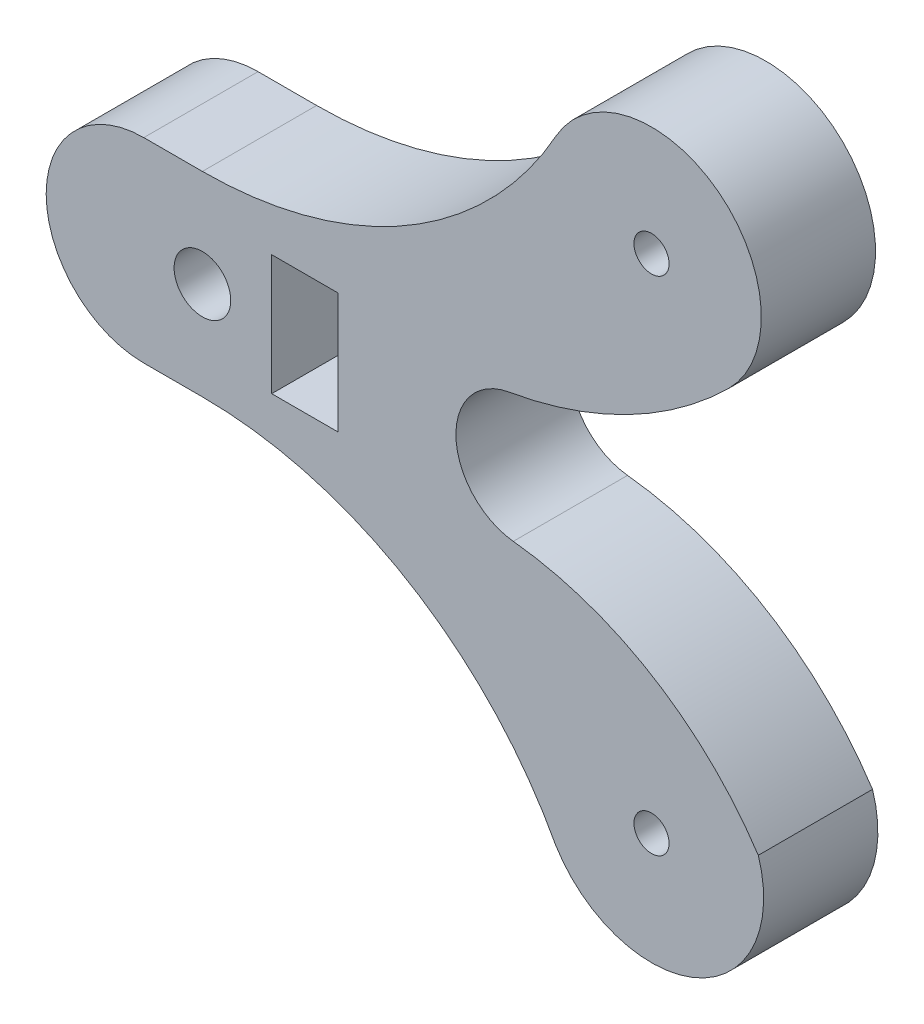
SolidWorks part; units mm, degrees
material "Acrylic (Medium-high impact)"
ref_plane "Front Plane" through (0, 0, 0) normal (0, 0, 1) x (1, 0, 0)
ref_plane "Top Plane" through (0, 0, 0) normal (0, 1, 0) x (1, 0, 0)
ref_plane "Right Plane" through (0, 0, 0) normal (1, 0, 0) x (0, 0, -1)
sketch "Sketch1" plane through (0, 0, 0) normal (0, 0, 1) x (1, 0, 0)
  line L0 (587.4699, 435.3658) -> (583.9197, 435.3658) construction
  line L1 (594.1695, 438.4484) -> (594.1695, 432.2832) construction
  line L2 (592.4695, 438.4484) -> (595.8695, 438.4484)
  line L3 (595.8695, 438.4484) -> (595.8695, 432.2832)
  line L4 (595.8695, 432.2832) -> (592.4695, 432.2832)
  line L5 (592.4695, 432.2832) -> (592.4695, 438.4484)
  line L6 (588.9197, 433.916) -> (588.9197, 430.3658) construction
  line L7 (588.9197, 436.8156) -> (588.9197, 440.3658) construction
  line L8 (592.4695, 435.3658) -> (595.8695, 435.3658) construction
  line L9 (588.9197, 440.3658) -> (585.9197, 440.3658)
  line L10 (611.9197, 448.2184) -> (611.9197, 422.5133) construction
  line L11 (611.9197, 422.5133) -> (611.9197, 425.8485) construction
  line L12 (601.9018, -564.6342) -> (601.9018, 49435.3658) construction
  line L13 (611.9197, 422.5133) -> (611.9197, 419.178) construction
  line L14 (588.9197, 430.3658) -> (585.9197, 430.3658)
  line L16 (611.9197, 448.2184) -> (611.9197, 451.5536) construction
  line L17 (611.9197, 448.2184) -> (611.9197, 444.8831) construction
  line L20 (606.9306, 435.3658) -> (50606.9306, 435.3658) construction
  circle A0 centre (611.9197, 448.2184) radius 0.9
  circle A1 centre (611.9197, 422.5133) radius 0.9
  circle A2 centre (588.9197, 435.3658) radius 1.4498
  arc A3 (585.9197, 440.3658) -> (585.9197, 430.3658) centre (585.9197, 435.3658) ccw
  arc A4 (607.0392, 451.01) -> (615.8671, 444.2145) centre (611.9197, 448.2184) cw
  arc A5 (588.9197, 440.3658) -> (607.0392, 451.01) centre (588.9197, 461.1101) ccw
  arc A6 (604.6283, 438.4325) -> (604.8418, 431.9206) centre (605.1913, 435.1915) ccw
  arc A7 (604.6283, 438.4325) -> (615.8671, 444.2145) centre (601.005, 459.2892) ccw
  arc A8 (604.8418, 431.9206) -> (617.3873, 424.2702) centre (603.0139, 414.8117) cw
  arc A9 (607.0155, 419.525) -> (617.3873, 424.2702) centre (611.9197, 422.5133) ccw
  arc A10 (588.9197, 430.3658) -> (607.0155, 419.525) centre (588.9197, 409.8424) cw
  point P33 (601.9036, 435.0837)
  point P35 (590.3695, 435.3658)
  dimension "D1" = 2.1
  dimension "D2" = 23
  dimension "D3" = 10
  dimension "D4" = 12.8525
  dimension "D5" = 12.8525
extrude "Boss-Extrude1" add sketch "Sketch1" along normal blind 5.85
